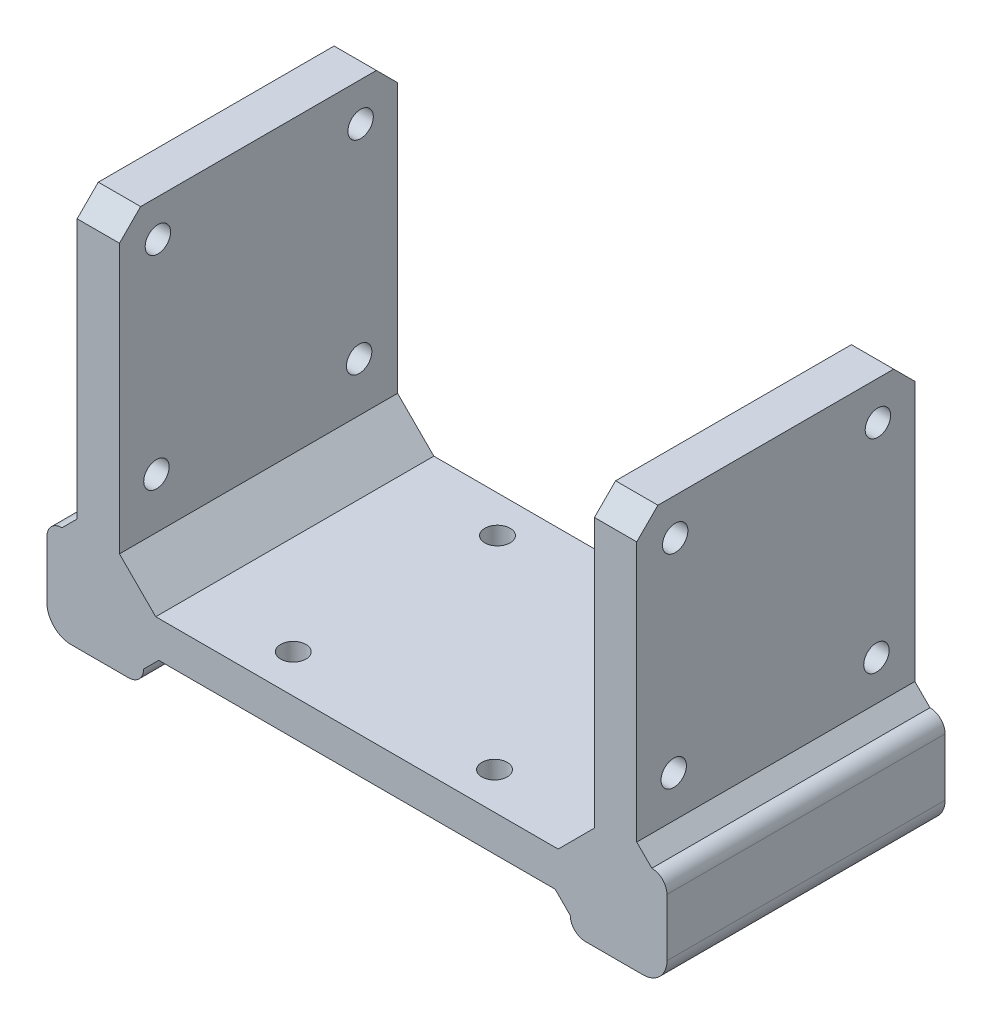
SolidWorks part; units mm, degrees
material "PA Type 6"
ref_plane "Płaszczyzna przednia" through (0, 0, 0) normal (0, 0, 1) x (1, 0, 0)
ref_plane "Płaszczyzna górna" through (0, 0, 0) normal (0, 1, 0) x (1, 0, 0)
ref_plane "Płaszczyzna prawa" through (0, 0, 0) normal (1, 0, 0) x (0, 0, -1)
sketch "Sketch1" plane through (0, 0, 0) normal (0, 1, 0) x (1, 0, 0)
  line L1 (0, 0) -> (92.56, 0)
  line L2 (0, 0) -> (0, 46)
  line L3 (0, 46) -> (92.56, 46)
  line L4 (92.56, 0) -> (92.56, 46)
  dimension "D1" = 92.56
  dimension "D2" = 46
extrude "Boss-Extrude1" add sketch "Sketch1" along normal blind 6
sketch "Sketch2" plane through (0, 6, 0) normal (0, 1, 0) x (1, 0, 0)
  line L0 (0, 0) -> (92.56, 0) construction
  line L1 (92.56, 46) -> (85.56, 46)
  line L2 (92.56, 46) -> (92.56, 0)
  line L3 (92.56, 0) -> (85.56, 0)
  line L4 (85.56, 46) -> (85.56, 0)
  line L6 (0, 46) -> (7, 46)
  line L7 (0, 46) -> (0, 0)
  line L8 (0, 0) -> (7, 0)
  line L9 (7, 46) -> (7, 0)
  dimension "D1" = 7
extrude "Boss-Extrude2" add sketch "Sketch2" along normal blind 54
sketch "Sketch3" plane through (92.56, 0, 0) normal (1, 0, 0) x (0, 0, -1)
  line L0 (0, 0) -> (46, 0) construction
  line L1 (23, 37) -> (23, 0) construction
  circle A0 centre (23, 37) radius 16
  dimension "D1" = 32
  dimension "D2" = 37
extrude "Cut-Extrude1" cut sketch "Sketch3" against normal through all
sketch "Sketch4" plane through (0, 6, 0) normal (0, 1, 0) x (1, 0, 0)
  line L0 (7, 46) -> (85.56, 0) construction
  line L1 (85.56, 0) -> (85.56, 46) construction
  line L2 (85.56, 46) -> (7, 0) construction
  circle A0 centre (46.28, 23) radius 16
  dimension "D1" = 32
extrude "Cut-Extrude2" cut sketch "Sketch4" against normal through all
sketch "Sketch5" plane through (0, 0, 0) normal (-1, 0, 0) x (0, 0, 1)
  line L0 (-46, 37) -> (-46, 60)
  line L1 (-46, 60) -> (0, 60)
  line L2 (0, 60) -> (0, 37)
  arc A0 (0, 37) -> (-46, 37) centre (-23, 37) ccw
extrude "Cut-Extrude3" [suppressed] cut sketch "Sketch5" against normal through all
hole_wizard "Ø4.2 (4.2) Diameter Hole1" positions "Sketch6" profile "Sketch7" hole size "Ø4.2" standard "DIN" end condition through all
sketch "Sketch6" plane through (0, 0, 0) normal (0, -1, 0) x (-1, 0, 0)
  point P0 (-63.1656, 39.6421)
  point P3 (-29.6379, 39.8856)
  point P6 (-29.3944, 6.3579)
  point P9 (-62.9221, 6.1144)
sketch "Sketch7" plane through (63.1656, 0, -39.6421) normal (1, 0, 0) x (0, 0, -1)
  line L0 (0, 0) -> (0, 60)
  line L1 (0, 60) -> (2.1, 60)
  line L2 (2.1, 60) -> (2.1, 0)
  line L5 (2.1, 0) -> (0, 0)
  line L11 (0, -6.35) -> (0, 107.95) construction
  dimension "Thru Hole Dia." = 4.2
  dimension "Thru Hole Depth" = 60
hole_wizard "Ø4.2 (4.2) Diameter Hole2" positions "Sketch8" profile "Sketch9" hole size "Ø4.2" standard "DIN" end condition through all
sketch "Sketch8" plane through (0, 0, 0) normal (-1, 0, 0) x (0, 0, 1)
  point P0 (-39.8856, 53.6421)
  point P3 (-6.3579, 53.8856)
  point P6 (-6.1144, 20.3579)
  point P9 (-39.6421, 20.1144)
sketch "Sketch9" plane through (0, 53.6421, -39.8856) normal (0, 1, 0) x (0, 0, 1)
  line L0 (0, 0) -> (0, 92.56)
  line L1 (0, 92.56) -> (2.1, 92.56)
  line L2 (2.1, 92.56) -> (2.1, 0)
  line L5 (2.1, 0) -> (0, 0)
  line L11 (0, -6.35) -> (0, 107.95) construction
  dimension "Thru Hole Dia." = 4.2
  dimension "Thru Hole Depth" = 92.56
chamfer "Chamfer1" distance 3.5 angle 45 4 edges at (3.5, 60, 0) (3.5, 60, -46) (89.06, 60, 0) (89.06, 60, -46)
chamfer "Chamfer2" distance 6 angle 45 2 edges at (7, 6, -23) (85.56, 6, -23)
sketch "Sketch10" plane through (0, 0, -46) normal (0, 0, -1) x (-1, 0, 0)
  line L0 (0, 11) -> (5, 11)
  line L1 (0, 56.5) -> (0, 0) construction
  line L2 (5, 11) -> (5, -5)
  line L3 (5, -5) -> (-11, -5)
  line L4 (-11, -5) -> (-11, 0)
  line L5 (-92.56, 0) -> (0, 0) construction
  line L6 (-11, 0) -> (0, 0)
  line L7 (0, 0) -> (0, 11)
  line L8 (-46.28, 6) -> (-46.28, 14.0709) construction
  line L9 (-79.56, 6) -> (-13, 6) construction
  line L10 (-81.56, 0) -> (-92.56, 0)
  line L11 (-81.56, -5) -> (-81.56, 0)
  line L12 (-97.56, -5) -> (-81.56, -5)
  line L13 (-97.56, 11) -> (-97.56, -5)
  line L14 (-92.56, 11) -> (-97.56, 11)
  line L15 (-92.56, 0) -> (-92.56, 11)
  dimension "D1" = 16
  dimension "D2" = 5
extrude "Boss-Extrude3" add sketch "Sketch10" against normal up to surface (46 mm away) up to face at (46.28, 26.2, 0)
fillet "Fillet1" radius 2.5 4 edges at (-5, 11, -23) (11, -5, -23) (97.56, 11, -23) (81.56, -5, -23)
chamfer "Chamfer3" distance 2.5 angle 45 4 edges at (92.56, 11, -23) (81.56, 0, -23) (11, 0, -23) (0, 11, -23)
fillet "Fillet2" radius 4 2 edges at (-5, -5, -23) (97.56, -5, -23)
sketch "Sketch11" plane through (0, 0, 0) normal (-1, 0, 0) x (0, 0, 1)
  circle A0 centre (-23, 37) radius 16 construction
  circle A1 centre (-23, 37) radius 16
extrude "Boss-Extrude4" add sketch "Sketch11" against normal blind 0.4
extrude "Boss-Extrude5" add sketch "Sketch11<2>" along normal blind 0.4 from surface starting at face at (7, 53.6421, -37.7856)
sketch "Sketch11<2>" plane through (0, 0, 0) normal (-1, 0, 0) x (0, 0, 1) same geometry as "Sketch11"
extrude "Boss-Extrude6" add sketch "Sketch11<3>" along normal blind 0.4 from surface starting at face at (92.56, 53.6421, -37.7856)
sketch "Sketch11<3>" plane through (0, 0, 0) normal (-1, 0, 0) x (0, 0, 1) same geometry as "Sketch11"
extrude "Boss-Extrude7" add sketch "Sketch11<4>" against normal blind 0.4 from surface starting at face at (85.56, 53.6421, -41.9856)
sketch "Sketch11<4>" plane through (0, 0, 0) normal (-1, 0, 0) x (0, 0, 1) same geometry as "Sketch11"
sketch "Sketch12" plane through (0, 0, 0) normal (0, -1, 0) x (1, 0, 0)
  circle A0 centre (46.28, -23) radius 16 construction
  circle A1 centre (46.28, -23) radius 16
extrude "Boss-Extrude8" add sketch "Sketch12" against normal blind 0.4
extrude "Boss-Extrude9" add sketch "Sketch12<2>" along normal blind 0.4 from surface starting at face at (63.1656, 6, -41.7421)
sketch "Sketch12<2>" plane through (0, 0, 0) normal (0, -1, 0) x (1, 0, 0) same geometry as "Sketch12"
